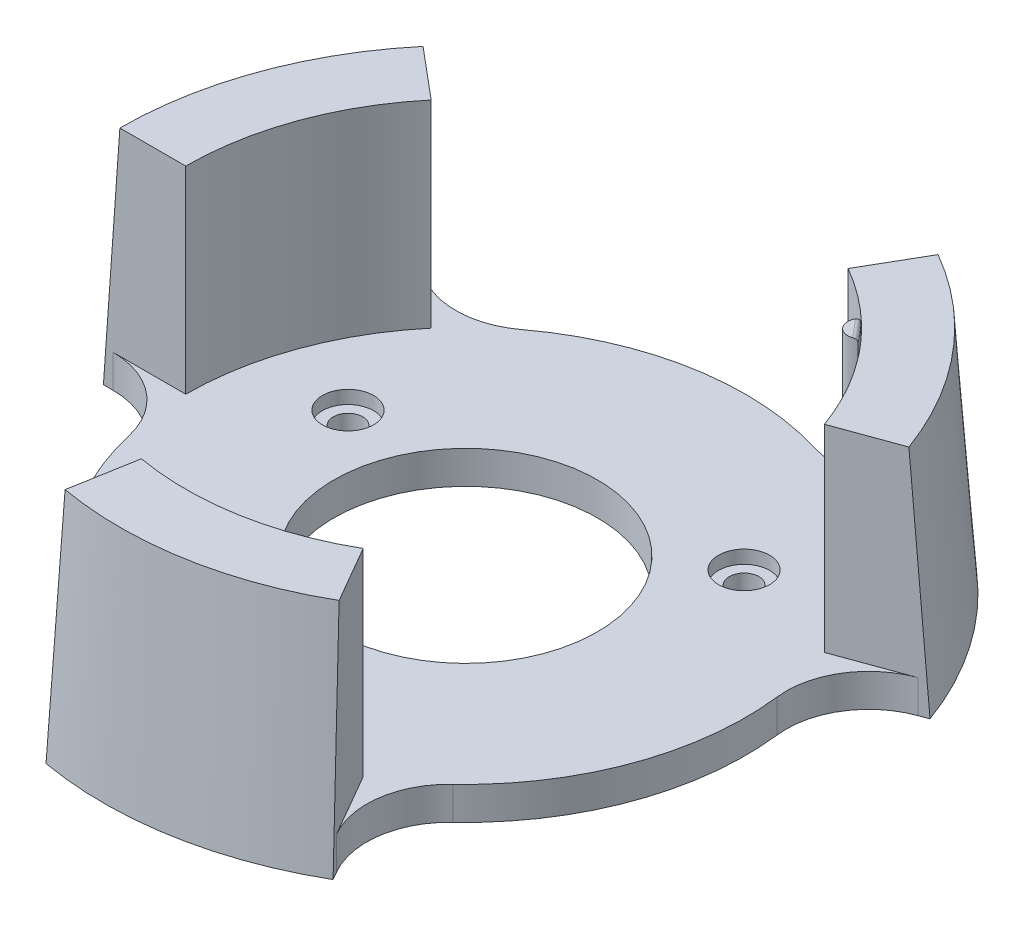
SolidWorks part; units mm, degrees
ref_plane "Front Plane" through (0, 0, 0) normal (0, 0, 1) x (1, 0, 0)
ref_plane "Top Plane" through (0, 0, 0) normal (0, 1, 0) x (1, 0, 0)
ref_plane "Right Plane" through (0, 0, 0) normal (1, 0, 0) x (0, 0, -1)
sketch "Sketch1" plane through (0, 0, 0) normal (0, 1, 0) x (1, 0, 0)
  circle A0 centre (0, 0) radius 8
  circle A1 centre (0, 0) radius 17
  dimension "D1" = 16
  dimension "D2" = 34
extrude "Boss-Extrude4" add sketch "Sketch1" along normal blind 2 contours A1 | A0
sketch "Sketch5" plane through (0, 0, 0) normal (0, 0, 1) x (1, 0, 0)
  line L0 (-17, 0) -> (-22, 0)
  line L1 (-17, 0) -> (-17, 14)
  line L2 (-17, 14) -> (-21, 14)
  line L3 (-21, 14) -> (-22, 0)
  line L4 (-17, 0) -> (17, 0) construction
  line L5 (0, 9.8137) -> (0, -8.5535) construction
  dimension "D1" = 14
  dimension "D2" = 5
  dimension "D3" = 4
revolve "Revolve2" add sketch "Sketch5" angle 40 about L5
pattern_circular "CirPattern1" count 3 over 360 about axis through (0, 2, 0) along (0, 1, 0) of "Revolve2"
fillet "Fillet1" radius 5 6 edges at (8.5, 1, 14.7224) (15.9748, 1, -5.8143) (8.5, 1, -14.7224) (-13.0228, 1, -10.9274) (-17, 1, 0) (-2.952, 1, 16.7417)
sketch "Sketch6" plane through (0, 2, 0) normal (0, 1, 0) x (1, 0, 0)
  line L0 (-15.9748, 5.8143) -> (20.5236, -7.47) construction
  line L1 (13.0228, 10.9274) -> (-17.0854, -14.3363) construction
  line L2 (2.952, -16.7417) -> (-4.6806, 26.545) construction
  arc A0 (-13.0228, 10.9274) -> (-17, 0) centre (0, 0) ccw construction
  arc A1 (15.9748, 5.8143) -> (8.5, 14.7224) centre (0, 0) ccw construction
  arc A2 (-2.952, -16.7417) -> (8.5, -14.7224) centre (0, 0) ccw construction
  circle A3 centre (0, 0) radius 12 construction
  point P19 (-11.2361, 4.0896)
  point P20 (2.0838, -11.8177)
  point P22 (0.0402, -0.0146)
  point P23 (9.1925, 7.7135)
  dimension "D1" = 24
sketch "Sketch18" plane through (0, 0, 0) normal (0, -1, 0) x (1, 0, 0)
  line L0 (13.0228, -10.9274) -> (-17.0854, 14.3363) construction
sketch "Sketch22" plane through (0, 14, 0) normal (0, 1, 0) x (1, 0, 0)
  line L0 (2.952, -16.7417) -> (3.6466, -20.681) construction
  arc A0 (-2.952, -16.7417) -> (8.5, -14.7224) centre (0, 0) ccw construction
  arc A1 (-3.6466, -20.681) -> (10.5, -18.1865) centre (0, 0) ccw construction
sketch "Sketch24" plane through (0, 2, 0) normal (0, 1, 0) x (1, 0, 0)
  arc A0 (12.5281, 11.4912) -> (13.4921, 10.3423) centre (13.0228, 10.9274) ccw
  arc A1 (15.9748, 5.8143) -> (8.5, 14.7224) centre (0, 0) ccw construction
  arc A2 (13.4921, 10.3423) -> (12.5281, 11.4912) centre (0, 0) ccw
extrude "Boss-Extrude6" add sketch "Sketch24" along normal blind 13
fillet "Fillet2" radius 0.25 1 edges at (13.0228, 15, -10.9274)
sketch "Sketch25" plane through (0, 2, 0) normal (0, 1, 0) x (1, 0, 0)
  circle A0 centre (2.0838, -11.8177) radius 0.9
  circle A1 centre (-11.2361, 4.0896) radius 0.9
  circle A2 centre (9.1925, 7.7135) radius 0.9
  dimension "D1" = 1.8
extrude "Cut-Extrude1" cut sketch "Sketch25" against normal through all
sketch "Sketch26" plane through (0, 2, 0) normal (0, 1, 0) x (1, 0, 0)
  circle A0 centre (2.0838, -11.8177) radius 1.55
  circle A1 centre (-11.2361, 4.0896) radius 1.55
  circle A2 centre (9.1925, 7.7135) radius 1.55
  dimension "D1" = 3.1
extrude "Cut-Extrude2" cut sketch "Sketch26" against normal blind 0.8
sketch "Sketch27" plane through (0, 2, 0) normal (0, 1, 0) x (1, 0, 0)
  line L0 (3.8203, -21.6658) -> (-2.952, 16.7417) construction
  arc A0 (-3.8203, -21.6658) -> (11, -19.0526) centre (0, 0) ccw construction
  arc A1 (4.9316, 16.269) -> (-10.1985, 13.6011) centre (0, 0) ccw construction
